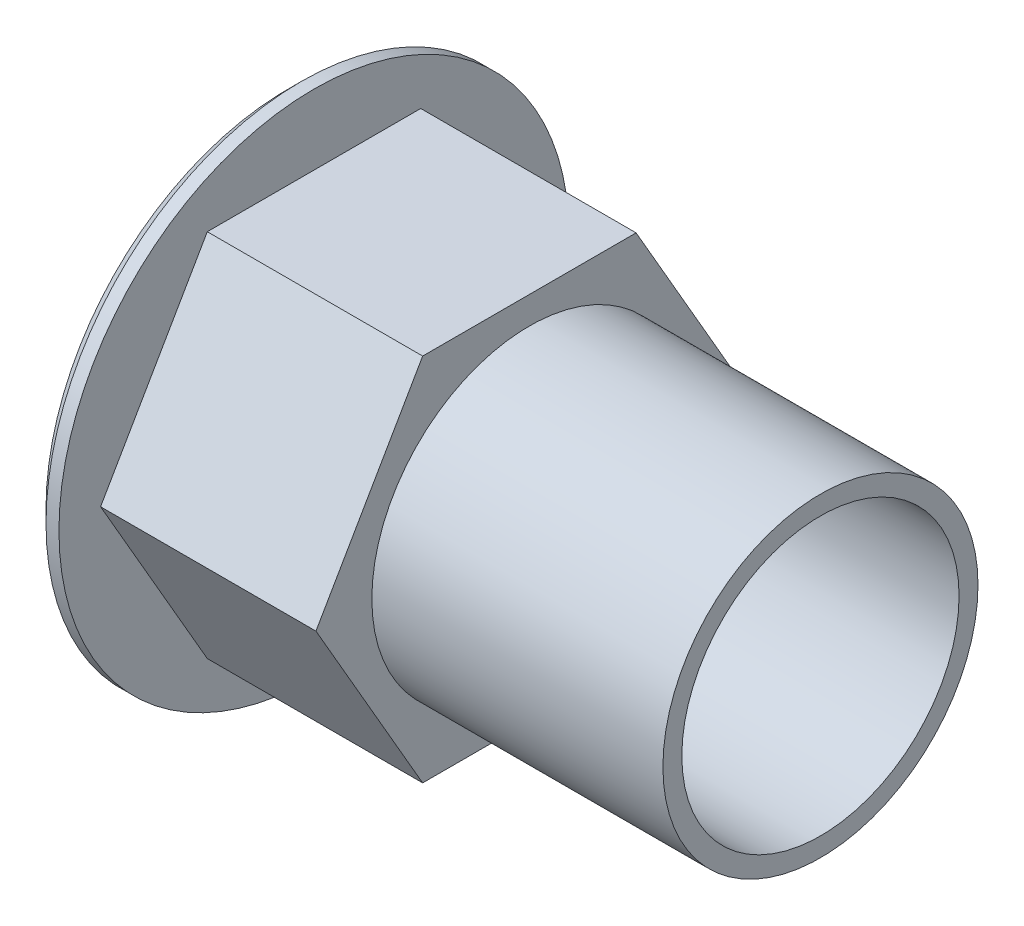
SolidWorks part; units mm, degrees
ref_plane "Front Plane" through (0, 0, 0) normal (0, 0, 1) x (1, 0, 0)
ref_plane "Top Plane" through (0, 0, 0) normal (0, 1, 0) x (1, 0, 0)
ref_plane "Right Plane" through (0, 0, 0) normal (1, 0, 0) x (0, 0, -1)
sketch "Sketch1" plane through (0, 0, 0) normal (0, 0, 1) x (1, 0, 0)
  line L0 (0, 0) -> (13.5536, 0) construction
  line L1 (0, 4.7625) -> (0, 8.3185)
  line L2 (0, 8.3185) -> (0.4445, 8.763)
  line L3 (0.4445, 8.763) -> (0.889, 8.763)
  line L4 (0.889, 8.763) -> (0.889, 5.4125)
  line L5 (0.889, 5.4125) -> (18.288, 5.4125)
  line L8 (18.288, 5.4125) -> (18.288, 4.7625)
  line L10 (0, 4.7625) -> (18.288, 4.7625)
  dimension "D3" = 135
  dimension "D4" = 0.4445
  dimension "D7" = 10.825
revolve "Revolve1" add sketch "Sketch1" angle 360 about L0
sketch "Sketch2" plane through (0.889, 0, 0) normal (1, 0, 0) x (0, 0, -1)
  line L1 (7.3323, 0) -> (3.6662, 6.35)
  line L2 (3.6662, 6.35) -> (-3.6662, 6.35)
  line L3 (-3.6662, 6.35) -> (-7.3323, 0)
  line L4 (-7.3323, 0) -> (-3.6662, -6.35)
  line L5 (-3.6662, -6.35) -> (3.6662, -6.35)
  line L6 (3.6662, -6.35) -> (7.3323, 0)
  circle A0 centre (0, 0) radius 6.35 construction
  circle A1 centre (0, 0) radius 5.4125 construction
  circle A2 centre (0, 0) radius 5.4125
  dimension "D" = 12.7
extrude "Extrude1" add sketch "Sketch2" along normal blind 7.399
surface "Surface-Offset1" [suppressed] parameters "D1"=0.254
equation "\"D1@Extrude1\" = \"A@Sketch1\"-(10/25.4)"
equation "\"D4@Sketch1\" = \"C@Sketch1\"/2"
equation "\"D7@Sketch1\" = \"Hole dia@Sketch1\"+(1.3/25.4)"
